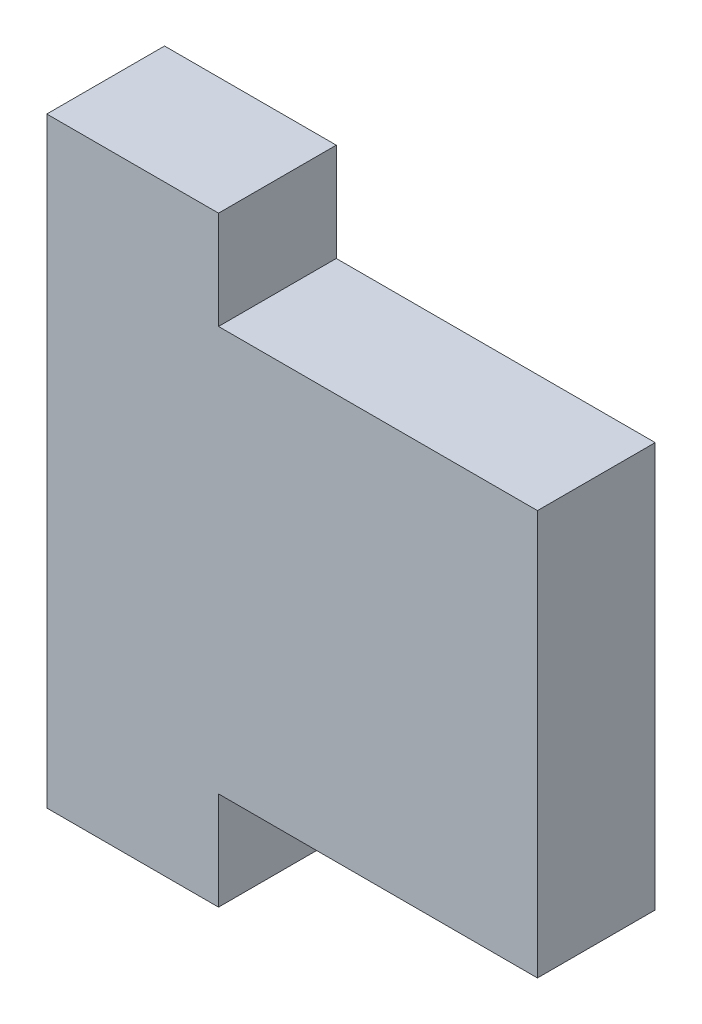
SolidWorks part; units mm, degrees
ref_plane "Front" through (0, 0, 0) normal (0, 0, 1) x (1, 0, 0)
ref_plane "Top" through (0, 0, 0) normal (0, 1, 0) x (1, 0, 0)
ref_plane "Right" through (0, 0, 0) normal (1, 0, 0) x (0, 0, -1)
ref_axis "side-side" through (80.9, 0, 0) along (-1, 0, 0)
ref_axis "up-down" through (0, 50, 0) along (0, -1, 0)
ref_axis "front-back" through (0, 0, -80.9) along (0, 0, 1)
sketch "Sketch1" plane through (0, 0, 0) normal (0, 0, 1) x (1, 0, 0)
  line L0 (-50.292, -10.4775) -> (-84.9208, -10.4775) construction
  line L1 (-55.626, 10.4775) -> (-72.136, 10.4775)
  line L2 (-55.626, 10.4775) -> (-55.626, -10.4775)
  line L3 (-55.626, -10.4775) -> (-72.136, -10.4775)
  line L4 (-81.026, 15.5575) -> (-81.026, -15.5575)
  line L5 (-50.292, 10.4775) -> (-84.9208, 10.4775) construction
  line L6 (-55.626, -10.4775) -> (-55.626, 10.4775) construction
  line L7 (-72.136, -10.4775) -> (-72.136, -15.5575)
  line L8 (-72.136, 15.5575) -> (-81.026, 15.5575)
  line L9 (-72.136, 15.5575) -> (-72.136, 10.4775)
  line L10 (-72.136, -15.5575) -> (-81.026, -15.5575)
  dimension "D1" = 25.4
  dimension "D2" = 8.89
  dimension "D3" = 5.08
  dimension "D4" = 5.08
extrude "Boss-Extrude1" add sketch "Sketch1" along normal mid plane 6.096
